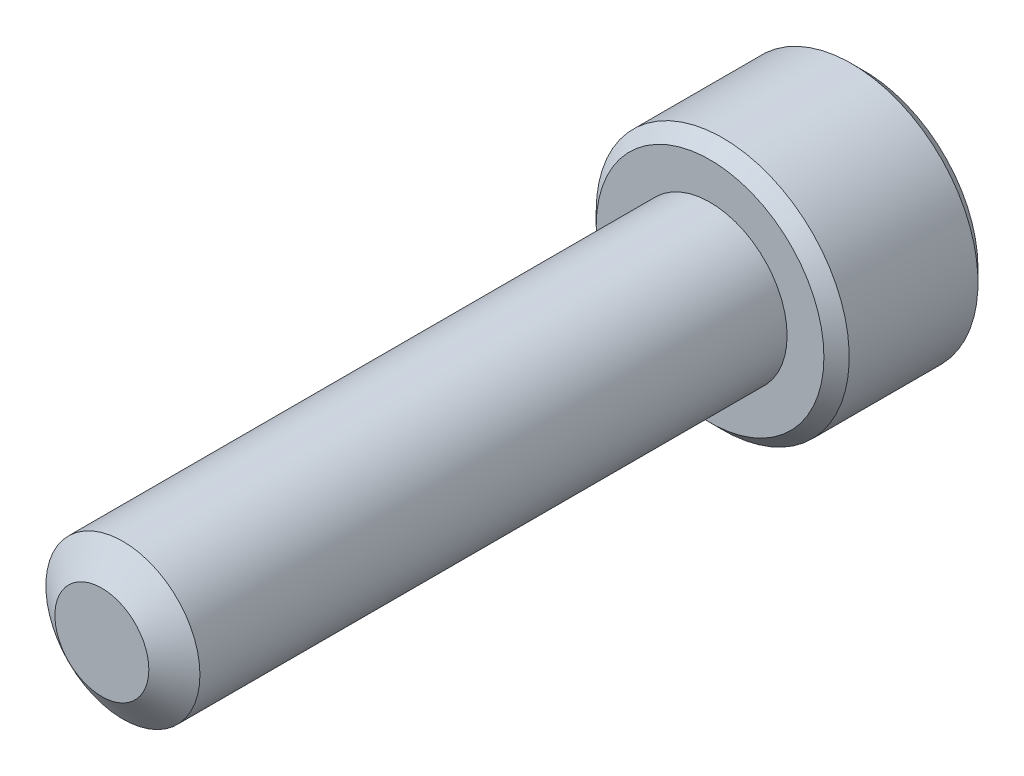
SolidWorks part; units mm, degrees
ref_plane "Front Plane" through (0, 0, 0) normal (0, 0, 1) x (1, 0, 0)
ref_plane "Top Plane" through (0, 0, 0) normal (0, 1, 0) x (1, 0, 0)
ref_plane "Right Plane" through (0, 0, 0) normal (1, 0, 0) x (0, 0, -1)
sketch "Sketch1" plane through (0, 0, 0) normal (0, 0, 1) x (1, 0, 0)
  circle A0 centre (0, 0) radius 2.413
  dimension "OD" = 4.826
extrude "Extrude1" add sketch "Sketch1" against normal blind 19.05
sketch "Sketch2" plane through (0, 0, 0) normal (0, 0, 1) x (1, 0, 0)
  circle A0 centre (0, 0) radius 2.413 construction
  circle A1 centre (0, 0) radius 2.413
curve "Helix/Spiral1" [suppressed] pitch 1.0583 height 20.1083 turns 19 parameters "pitch"=1.0583
sketch "Sketch3" plane through (0, 0, 0) normal (1, 0, 0) x (0, 0, -1)
  line L0 (-0.926, 2.413) -> (-0.5292, 1.7256)
  line L1 (-0.5292, 1.7256) -> (-0.3969, 1.7256)
  line L2 (-0.3969, 1.7256) -> (0, 2.413)
  line L3 (-0.926, 2.413) -> (0, 2.413)
  line L4 (-0.463, 2.413) -> (-0.463, 1.7256) construction
  line L5 (-0.7276, 2.0693) -> (-0.1984, 2.0693) construction
  line L6 (0, 2.413) -> (0, -2.413) construction
  dimension "D1" = 0.1323
  dimension "D2" = 0.5292
  dimension "D3" = 60
sweep "Cut-Sweep1" [suppressed] cut profiles "Sketch3" path "Helix/Spiral1"
sketch "Sketch4" plane through (0, 0, 0) normal (1, 0, 0) x (0, 0, -1)
  line L0 (0.6592, 2.413) -> (0, 1.4716)
  line L1 (0, 1.4716) -> (0, 2.413)
  line L2 (0.6592, 2.413) -> (0, 2.413)
  line L3 (-0.926, 2.413) -> (0, 2.413) construction
  line L4 (0, 0) -> (7.0209, 0) construction
  dimension "D1" = 55
  dimension "D2" = 0.254
revolve "Cut-Revolve1" cut sketch "Sketch4" angle 360 about L4
sketch "Sketch5" [suppressed] plane through (0, 0, 0) normal (1, 0, 0) x (0, 0, -1)
  line L0 (19.05, -1.7471) -> (19.05, 1.7217) construction
  line L1 (19.05, 2.54) -> (87.4327, 2.54)
  line L2 (19.05, 2.54) -> (19.05, 0)
  line L3 (19.05, 0) -> (87.3125, 0)
  line L4 (87.3125, 2.2098) -> (87.3125, 0)
  line L5 (87.4327, 2.54) -> (87.3125, 2.2098)
  line L6 (0, 0) -> (9.9695, 0) construction
  point P3 (87.3125, 2.54)
  point P10 (87.3125, 2.54)
  dimension "D1" = 0.3302
  dimension "Thread min" = 87.3125
  dimension "D2" = 0.127
  dimension "D3" = 20
revolve "partially thread" [suppressed] add sketch "Sketch5" angle 360 about L6
sketch "Sketch6" plane through (0, 0, -19.05) normal (0, 0, -1) x (-1, 0, 0)
  circle A0 centre (0, 0) radius 3.9624
  dimension "head dia" = 7.9248
extrude "Extrude2" add sketch "Sketch6" along normal blind 4.826
sketch "Sketch7" plane through (0, 0, -23.876) normal (0, 0, -1) x (-1, 0, 0)
  line L1 (0, 2.2914) -> (-1.9844, 1.1457)
  line L2 (-1.9844, 1.1457) -> (-1.9844, -1.1457)
  line L3 (-1.9844, -1.1457) -> (0, -2.2914)
  line L4 (0, -2.2914) -> (1.9844, -1.1457)
  line L5 (1.9844, -1.1457) -> (1.9844, 1.1457)
  line L6 (1.9844, 1.1457) -> (0, 2.2914)
  circle A0 centre (0, 0) radius 1.9844 construction
  dimension "hex dia" = 3.9688
extrude "Cut-Extrude1" cut sketch "Sketch7" against normal blind 2.9766
sketch "Sketch8" plane through (0, 0, -23.876) normal (0, 0, -1) x (-1, 0, 0)
  circle A0 centre (0, 0) radius 2.2914
extrude "Cut-Extrude2" cut sketch "Sketch8" against normal through all draft 45
chamfer "Chamfer1" distance 0.3962 angle 45 2 edges at (-3.9624, 0, -23.876) (-3.9624, 0, -19.05)
sketch "Sketch9" plane through (0, 0, 0) normal (1, 0, 0) x (0, 0, -1)
  line L0 (0, 2.413) -> (0, -2.413) construction
  line L1 (5.8208, 2.413) -> (5.8208, -2.413) construction
  dimension "D1" = 5.8208
equation "\"D3@Helix/Spiral1\" = \"screw length@Extrude1\"+\"pitch@Helix/Spiral1\""
equation "\"D1@Sketch3\" = \"pitch@Helix/Spiral1\"*.125"
equation "\"D2@Sketch3\" = \"pitch@Helix/Spiral1\"*.5"
equation "\"D1@Cut-Extrude1\" = \"hex dia@Sketch7\"*.75"
equation "\"D1@Chamfer1\" = \"head dia@Sketch6\"*.05"
equation "\"D1@Sketch9\" = \"pitch@Helix/Spiral1\"*5.5"
